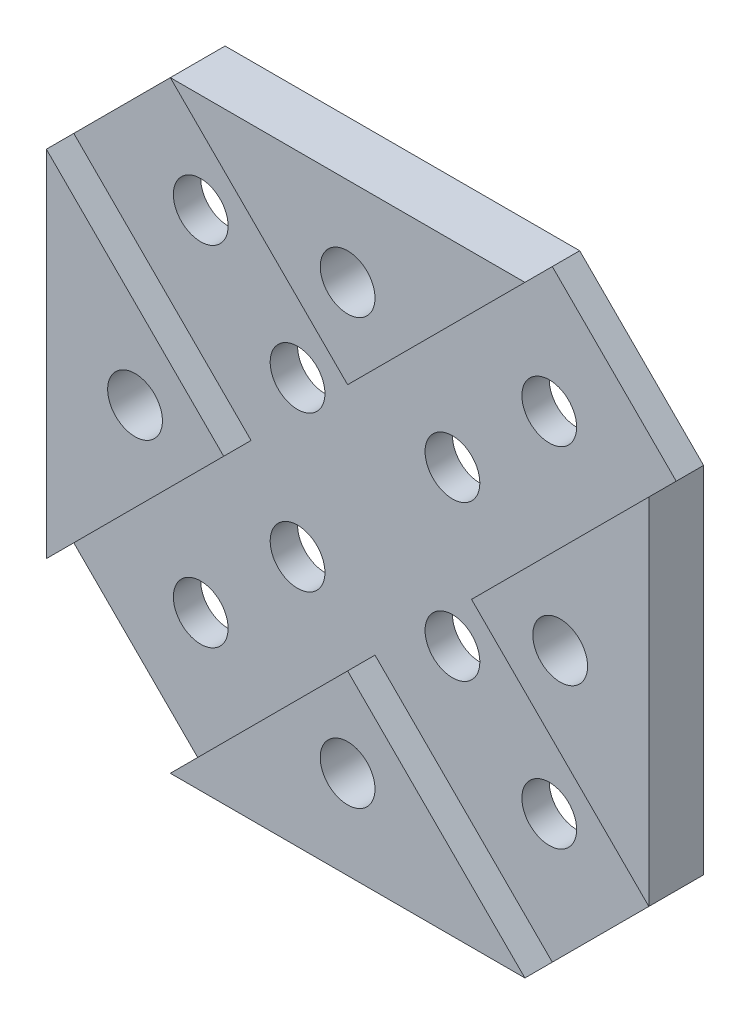
SolidWorks part; units mm, degrees
ref_plane "Plan de face" through (0, 0, 0) normal (0, 0, 1) x (1, 0, 0)
ref_plane "Plan de dessus" through (0, 0, 0) normal (0, 1, 0) x (1, 0, 0)
ref_plane "Plan de droite" through (0, 0, 0) normal (1, 0, 0) x (0, 0, -1)
sketch "Esquisse1" plane through (0, 0, 0) normal (0, 0, 1) x (1, 0, 0)
  line L0 (-55, 32.3726) -> (-32.3726, 55)
  line L1 (55, -55) -> (-55, -55)
  line L2 (55, -55) -> (55, 55)
  line L3 (55, 55) -> (-55, 55)
  line L4 (-55, -55) -> (-55, 55)
  line L5 (55, -55) -> (-55, 55) construction
  line L6 (55, 55) -> (-55, -55) construction
  line L7 (0, -55) -> (0, 55) construction
  line L8 (-55, 0) -> (55, 0) construction
  line L9 (55, 32.3726) -> (32.3726, 55)
  line L10 (55, -32.3726) -> (32.3726, -55)
  line L11 (-55, -32.3726) -> (-32.3726, -55)
  point P0 (0, 0)
  point P23 (0, 0)
  point P26 (0, 0)
  point P29 (0, 0)
  point P32 (0, 0)
  dimension "D2" = 110
  dimension "D3" = 32
  dimension "D4" = 45
  dimension "D7" = 4
extrude "Boss.-Extru.1" add sketch "Esquisse1" along normal blind 10 contours L4 L11 L1 L10 L2 L9 L3 L0 region at (0, 0, 0)
sketch "Esquisse3" plane through (0, 0, 10) normal (0, 0, 1) x (1, 0, 0)
  line L0 (-55, 32.3726) -> (-32.3726, 55)
  line L1 (-32.3726, 55) -> (0, 22.6274)
  line L2 (55, -32.3726) -> (32.3726, -55)
  line L3 (32.3726, -55) -> (0, -22.6274)
  line L4 (-55, 32.3726) -> (-32.3726, 55) construction
  line L5 (55, -32.3726) -> (32.3726, -55) construction
  line L6 (-55, -32.3726) -> (-32.3726, -55)
  line L7 (-32.3726, -55) -> (0, -22.6274)
  line L9 (32.3726, 55) -> (0, 22.6274)
  line L10 (32.3726, 55) -> (55, 32.3726)
  line L11 (22.6274, 0) -> (55, -32.3726)
  line L12 (-22.6274, 0) -> (-55, -32.3726)
  line L13 (22.6274, 0) -> (55, 32.3726)
  line L14 (-22.6274, 0) -> (-55, 32.3726)
  point P7 (-43.6863, 43.6863)
extrude "Enlèv. mat.-Extru.1" cut sketch "Esquisse3" against normal blind 5
sketch "Esquisse4" plane through (0, 0, 5) normal (0, 0, 1) x (1, 0, 0)
  line L0 (-43.6863, 43.6863) -> (43.6863, -43.6863) construction
  line L1 (-32.3726, 55) -> (-55, 32.3726) construction
  line L2 (32.3726, -55) -> (55, -32.3726) construction
  line L3 (-43.6863, -43.6863) -> (43.6863, 43.6863) construction
  line L4 (-55, -32.3726) -> (-32.3726, -55) construction
  line L5 (55, 32.3726) -> (32.3726, 55) construction
  line L6 (0, 0) -> (-14.1421, 14.1421) construction
  line L7 (0, 0) -> (14.1421, 14.1421) construction
  line L8 (0, 22.6274) -> (0, 55) construction
  line L9 (32.3726, 55) -> (-32.3726, 55) construction
  circle A1 centre (-31.8198, 31.8198) radius 5
  circle A2 centre (-14.1421, 14.1421) radius 5
  circle A3 centre (31.8198, 31.8198) radius 5
  circle A4 centre (14.1421, 14.1421) radius 5
  circle A5 centre (31.8198, -31.8198) radius 5
  circle A6 centre (14.1421, -14.1421) radius 5
  circle A7 centre (-31.8198, -31.8198) radius 5
  circle A8 centre (-14.1421, -14.1421) radius 5
  circle A9 centre (0, 38.8137) radius 5
  circle A10 centre (38.8137, 0) radius 5
  circle A11 centre (0, -38.8137) radius 5
  circle A12 centre (-38.8137, 0) radius 5
  point P49 (0, 0)
  dimension "D1" = 10
  dimension "D2" = 10
  dimension "D7" = 10
  dimension "D3" = 45
  dimension "D4" = 20
  dimension "D6" = 90
  dimension "D5" = 4
  dimension "D8" = 4
extrude "Enlèv. mat.-Extru.2" cut sketch "Esquisse4" against normal through all and the other way through all
